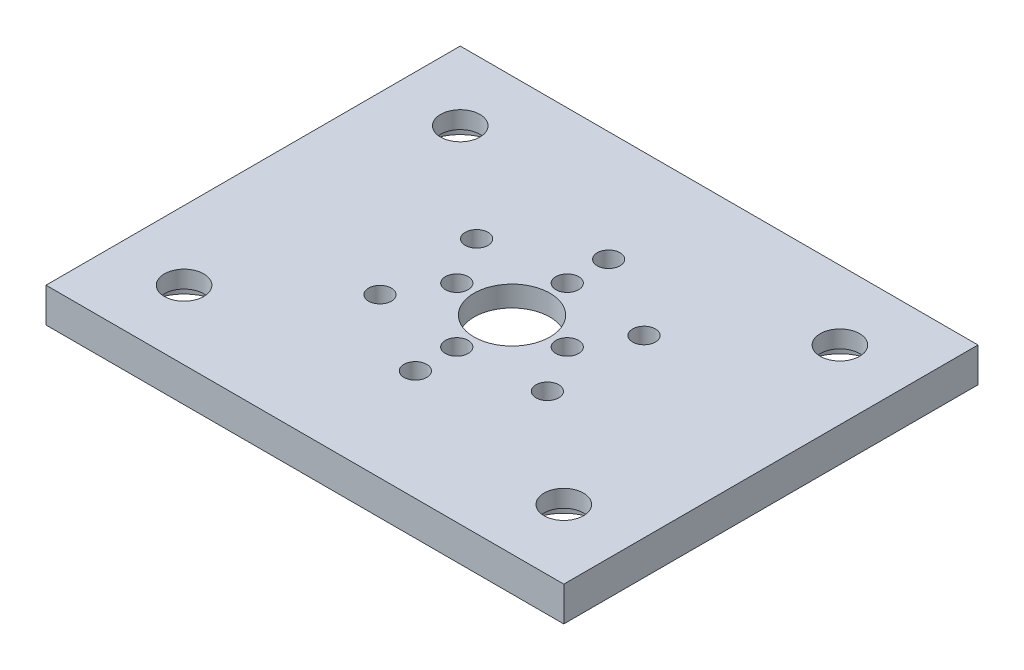
SolidWorks part; units mm, degrees
note: '?' marks a value the reader was unsure of.
material "Thornel Mat VMA"
ref_plane "前视基准面" through (0, 0, 0) normal (0, 0, 1) x (1, 0, 0)
ref_plane "上视基准面" through (0, 0, 0) normal (0, 1, 0) x (1, 0, 0)
ref_plane "右视基准面" through (0, 0, 0) normal (1, 0, 0) x (0, 0, -1)
sketch "草图1" plane through (0, 0, 0) normal (0, 1, 0) x (1, 0, 0)
  line L1 (0, 0) -> (75, 0)
  line L2 (0, 0) -> (0, 60)
  line L3 (0, 60) -> (75, 60)
  line L4 (75, 0) -> (75, 60)
  dimension "D1" = 75
  dimension "D2" = 60
extrude "凸台-拉伸1" add sketch "草图1" along normal blind 5
sketch "草图2" plane through (0, 5, 0) normal (0, 1, 0) x (1, 0, 0)
  line L0 (0, 0) -> (75, 0) construction
  line L1 (0, 60) -> (20, 60)
  line L2 (0, 60) -> (0, 0)
  line L3 (0, 0) -> (20, 0)
  line L4 (20, 60) -> (20, 0)
  line L5 (0, 40) -> (20, 40)
  line L6 (75, 60) -> (55, 60)
  line L7 (75, 60) -> (75, 0)
  line L8 (75, 0) -> (55, 0)
  line L9 (55, 60) -> (55, 0)
  line L10 (0, 20) -> (20, 20)
  line L11 (55, 40) -> (75, 40)
  line L12 (55, 20) -> (75, 20)
  line L13 (0, 0) -> (20, 20)
  line L14 (0, 60) -> (20, 40)
  line L15 (75, 60) -> (55, 40)
  line L16 (75, 0) -> (55, 20)
  dimension "D1" = 20
  dimension "D2" = 20
  dimension "D3" = 20
  dimension "D4" = 20
  dimension "D5" = 20
  dimension "D6" = 20
sketch "草图4" plane through (0, 5, 0) normal (0, 1, 0) x (1, 0, 0)
  line L0 (0, 60) -> (20, 40) construction
  line L1 (0, 0) -> (20, 20) construction
  line L2 (75, 0) -> (55, 20) construction
  line L3 (75, 60) -> (55, 40) construction
  point P0 (10, 50)
  point P4 (10, 10)
  point P8 (65, 10)
  point P12 (65, 50)
hole_wizard "孔1" positions "草图4" profile "草图5" legacy end condition up to next
sketch "草图5" plane through (10, 5, -50) normal (1, 0, 0) x (0, 0, 1)
  line L0 (0, 0) -> (0, 5)
  line L1 (0, 5) -> (2.85, 5)
  line L2 (2.85, 5) -> (2.85, 0)
  line L3 (2.85, 0) -> (0, 0)
  line L4 (0, 110) -> (0, -10) construction
  dimension "直径" = 5.7
  dimension "深度" = 5
sketch "草图6" plane through (0, 5, 0) normal (0, 1, 0) x (1, 0, 0)
  line L0 (20, 30) -> (55, 30)
  line L1 (20, 60) -> (20, 0) construction
  line L2 (55, 60) -> (55, 0) construction
  circle A0 centre (37.5, 30) radius 5.5
  dimension "D1" = 11
extrude "切除-拉伸1" cut sketch "草图6" against normal blind 10 contours L0 A0 | L0 A0
sketch "草图7" plane through (0, 5, 0) normal (0, 1, 0) x (1, 0, 0)
  circle A0 centre (37.5, 30) radius 14
  dimension "D1" = 28
sketch "草图8" plane through (0, 5, 0) normal (0, 1, 0) x (1, 0, 0)
  circle A0 centre (37.5, 30) radius 14 construction
  point P0 (37.5, 44)
hole_wizard "孔2" positions "草图8" profile "草图9" legacy end condition up to next
sketch "草图9" plane through (37.5, 5, -44) normal (1, 0, 0) x (0, 0, 1)
  line L0 (0, 0) -> (0, 5)
  line L1 (0, 5) -> (1.65, 5)
  line L2 (1.65, 5) -> (1.65, 0)
  line L3 (1.65, 0) -> (0, 0)
  line L4 (0, 110) -> (0, -10) construction
  dimension "直径" = 3.3
  dimension "深度" = 5
ref_axis "基准轴1" through (37.5, 5, -30) along (0, 1, 0)?
pattern_circular "阵列(圆周)1" count 6 every 60 about axis through (37.5, 0, -30) along (0, 1, 0) of "孔2"
sketch "草图11" plane through (0, 0, 0) normal (0, -1, 0) x (-1, 0, 0)
  line L0 (0, 0) -> (-20, 20) construction
  line L1 (0, 60) -> (-20, 40) construction
  line L2 (-75, 60) -> (-55, 40) construction
  line L3 (-75, 0) -> (-55, 20) construction
  point P0 (-10, 10)
  point P4 (-10, 50)
  point P8 (-65, 50)
  point P12 (-65, 10)
hole_wizard "孔3" positions "草图11" profile "草图12" legacy
sketch "草图12" plane through (10, 0, -10) normal (1, 0, 0) x (0, 0, -1)
  line L0 (0, 0) -> (0, 2.5)
  line L1 (0, 2.5) -> (5.5, 2.5)
  line L2 (5.5, 2.5) -> (5.5, 0)
  line L3 (5.5, 0) -> (0, 0)
  line L4 (0, 110) -> (0, -10) construction
  dimension "直径" = 11
  dimension "深度" = 2.5
sketch "草图13" plane through (0, 5, 0) normal (0, 1, 0) x (1, 0, 0)
  circle A0 centre (37.5, 30) radius 11
  circle A1 centre (37.5, 30) radius 8
  dimension "D1" = 22
  dimension "D2" = 16
sketch "草图14" plane through (0, 5, 0) normal (0, 1, 0) x (1, 0, 0)
  circle A0 centre (37.5, 30) radius 8 construction
  point P0 (29.5, 30)
  point P4 (37.5, 38)
  point P6 (45.5, 30)
  point P8 (37.5, 22)
hole_wizard "孔4" positions "草图14" profile "草图15" legacy end condition up to next
sketch "草图15" plane through (29.5, 5, -30) normal (1, 0, 0) x (0, 0, 1)
  line L0 (0, 0) -> (0, 5)
  line L1 (0, 5) -> (1.65, 5)
  line L2 (1.65, 5) -> (1.65, 0)
  line L3 (1.65, 0) -> (0, 0)
  line L4 (0, 110) -> (0, -10) construction
  dimension "直径" = 3.3
  dimension "深度" = 5
sketch "草图16" plane through (0, 5, 0) normal (0, 1, 0) x (1, 0, 0)
  circle A0 centre (37.5, 30) radius 11
  dimension "D1" = 22
hole_wizard "孔5" positions "草图17" profile "草图18" legacy
sketch "草图17" plane through (0, 0, 0) normal (0, -1, 0) x (-1, 0, 0)
  point P0 (-37.5, 30)
sketch "草图18" plane through (37.5, 0, -30) normal (1, 0, 0) x (0, 0, -1)
  line L0 (0, 0) -> (0, 2)
  line L1 (0, 2) -> (11.5, 2)
  line L2 (11.5, 2) -> (11.5, 0)
  line L3 (11.5, 0) -> (0, 0)
  line L4 (0, 110) -> (0, -10) construction
  dimension "直径" = 23
  dimension "深度" = 2
